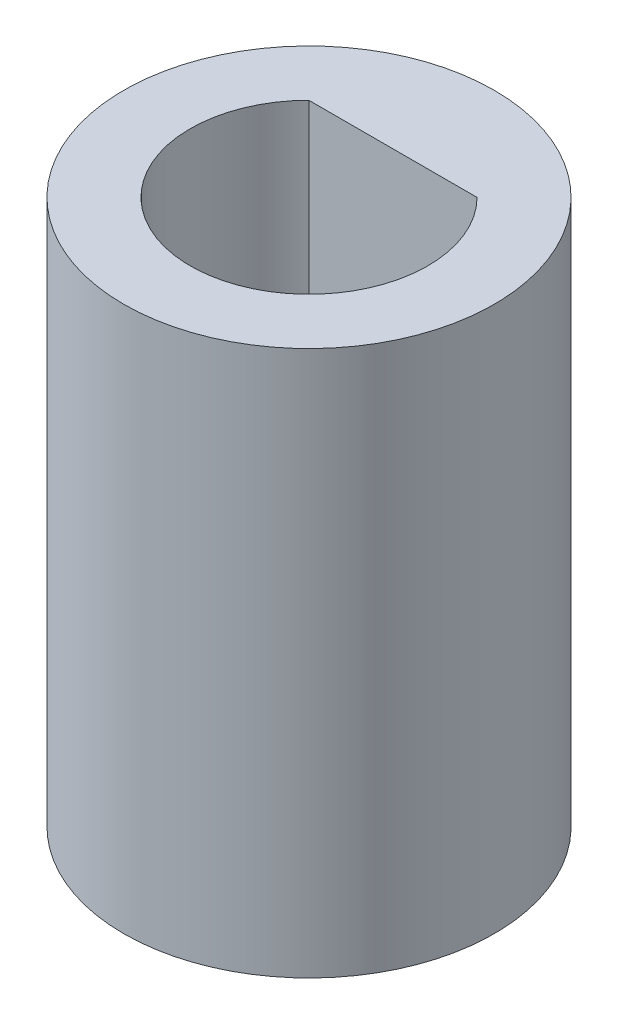
SolidWorks part; units mm, degrees
ref_plane "Front Plane" through (0, 0, 0) normal (0, 0, 1) x (1, 0, 0)
ref_plane "Top Plane" through (0, 0, 0) normal (0, 1, 0) x (1, 0, 0)
ref_plane "Right Plane" through (0, 0, 0) normal (1, 0, 0) x (0, 0, -1)
sketch "Sketch1" plane through (0, 0, 0) normal (0, 1, 0) x (1, 0, 0)
  line L0 (-2.5308, 2.525) -> (2.5308, 2.525) construction
  circle A0 centre (0, 0) radius 5.575
  circle A1 centre (0, 0) radius 3.575 construction
  arc A2 (-2.5308, 2.525) -> (2.5308, 2.525) centre (0, 0) ccw construction
  point P6 (0, -3.575)
  dimension "D1" = 7.15
  dimension "D2" = 2
  dimension "D3" = 6.1
extrude "Boss-Extrude1" add sketch "Sketch1" against normal blind 16.4
ref_plane "Plane1" through (0, 0, 0) normal (0, 1, 0) x (1, 0, 0)
sketch "Sketch3" plane through (0, 0, 0) normal (0, 1, 0) x (1, 0, 0)
  line L0 (-2.5308, 2.525) -> (2.5308, 2.525) construction
  line L1 (-2.5308, 2.525) -> (2.5308, 2.525)
  circle A0 centre (0, 0) radius 3.575 construction
  arc A1 (-2.5308, 2.525) -> (2.5308, 2.525) centre (0, 0) ccw
extrude "Cut-Extrude1" cut sketch "Sketch3" against normal through all
